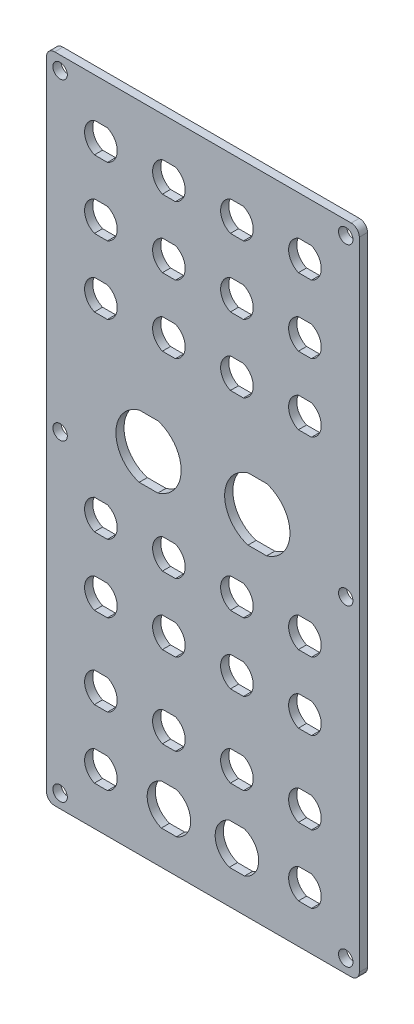
SolidWorks part; units mm, degrees
ref_plane "Front Plane" through (0, 0, 0) normal (0, 0, 1) x (1, 0, 0)
ref_plane "Top Plane" through (0, 0, 0) normal (0, 1, 0) x (1, 0, 0)
ref_plane "Right Plane" through (0, 0, 0) normal (1, 0, 0) x (0, 0, -1)
sketch "Sketch1" plane through (0, 0, 0) normal (0, 0, 1) x (1, 0, 0)
  line L1 (0, 0) -> (115, 0)
  line L2 (0, 0) -> (0, 240)
  line L3 (0, 240) -> (115, 240)
  line L4 (115, 0) -> (115, 240)
  dimension "D1" = 240
  dimension "D2" = 115
extrude "Boss-Extrude1" add sketch "Sketch1" along normal blind 3
sketch "Sketch2" plane through (0, 0, 3) normal (0, 0, 1) x (1, 0, 0)
  line L0 (20, 14.5) -> (20, 25.5) construction
  line L1 (22.3979, 25.5) -> (17.6021, 25.5)
  line L2 (22.3979, 14.5) -> (17.6021, 14.5)
  line L3 (0, 0) -> (115, 0) construction
  line L4 (0, 240) -> (0, 0) construction
  arc A0 (17.6021, 25.5) -> (17.6021, 14.5) centre (20, 20) ccw
  arc A1 (22.3979, 14.5) -> (22.3979, 25.5) centre (20, 20) ccw
  point P7 (20, 20)
  dimension "D2" = 12
  dimension "D1" = 11
  dimension "D3" = 20
  dimension "D4" = 20
extrude "Cut-Extrude1" cut sketch "Sketch2" against normal up to surface (3 mm away) up to face at (57.5, 120, 0)
pattern_linear "LPattern1" count 4 spacing 25 along (1, 0, 0) count 2 spacing 25 along (0, 1, 0) skipping (1, 0), (2, 0) of "Cut-Extrude1"
sketch "Sketch3" plane through (0, 0, 3) normal (0, 0, 1) x (1, 0, 0)
  line L0 (0, 120) -> (115, 120) construction
  line L1 (0, 240) -> (0, 0) construction
  line L2 (115, 0) -> (115, 240) construction
  line L3 (17.6021, 14.5) -> (22.3979, 14.5) construction
  line L4 (22.3979, 25.5) -> (17.6021, 25.5) construction
  line L5 (17.6021, 14.5) -> (22.3979, 14.5) construction
  line L6 (22.3979, 25.5) -> (17.6021, 25.5) construction
  line L7 (22.3979, 214.5) -> (17.6021, 214.5)
  line L8 (17.6021, 225.5) -> (22.3979, 225.5)
  arc A0 (17.6021, 25.5) -> (17.6021, 14.5) centre (20, 20) ccw construction
  arc A1 (22.3979, 14.5) -> (22.3979, 25.5) centre (20, 20) ccw construction
  arc A2 (17.6021, 25.5) -> (17.6021, 14.5) centre (20, 20) ccw construction
  arc A3 (22.3979, 14.5) -> (22.3979, 25.5) centre (20, 20) ccw construction
  arc A4 (22.3979, 225.5) -> (22.3979, 214.5) centre (20, 220) cw
  arc A5 (17.6021, 214.5) -> (17.6021, 225.5) centre (20, 220) cw
extrude "Cut-Extrude2" cut sketch "Sketch3" against normal up to surface (3 mm away) up to face at (95, 20, 0)
pattern_linear "LPattern2" count 4 spacing 25 along (1, 0, 0) count 3 spacing 25 along (0, -1, 0) of "Cut-Extrude2"
sketch "Sketch4" plane through (0, 0, 3) normal (0, 0, 1) x (1, 0, 0)
  line L0 (20, 25.5) -> (20, 14.5) construction
  line L1 (22.3979, 25.5) -> (17.6021, 25.5) construction
  line L2 (17.6021, 14.5) -> (22.3979, 14.5) construction
  line L3 (39, 45) -> (51, 45) construction
  line L4 (42.2161, 27.5) -> (47.7839, 27.5)
  line L5 (45, 12.5) -> (45, 27.5) construction
  line L6 (47.7839, 12.5) -> (42.2161, 12.5)
  arc A0 (42.2161, 27.5) -> (42.2161, 12.5) centre (45, 20) ccw
  arc A1 (42.6021, 50.5) -> (42.6021, 39.5) centre (45, 45) ccw construction
  arc A2 (47.3979, 39.5) -> (47.3979, 50.5) centre (45, 45) ccw construction
  arc A3 (47.7839, 12.5) -> (47.7839, 27.5) centre (45, 20) ccw
  point P16 (45, 45)
  point P17 (20, 20)
  point P24 (45, 20)
  point P25 (45, 14.7085)
  dimension "D1" = 16
  dimension "D2" = 15
extrude "Cut-Extrude3" cut sketch "Sketch4" against normal up to surface (3 mm away) up to face at (45, 220, 0)
ref_plane "Plane2" through (57.5, 0, 0) normal (-1, 0, 0) x (0, 0, 1)
mirror "Mirror2" about plane through (57.5, 0, 0) normal (-1, 0, 0) of "Cut-Extrude3"
sketch "Sketch5" plane through (0, 0, 3) normal (0, 0, 1) x (1, 0, 0)
  line L0 (14, 45) -> (26, 45) construction
  line L1 (22.3979, 80.5) -> (17.6021, 80.5)
  line L2 (20, 69.5) -> (20, 80.5) construction
  line L3 (17.6021, 69.5) -> (22.3979, 69.5)
  arc A0 (17.6021, 80.5) -> (17.6021, 69.5) centre (20, 75) ccw
  arc A1 (17.6021, 50.5) -> (17.6021, 39.5) centre (20, 45) ccw construction
  arc A2 (22.3979, 39.5) -> (22.3979, 50.5) centre (20, 45) ccw construction
  arc A3 (22.3979, 69.5) -> (22.3979, 80.5) centre (20, 75) ccw
  point P10 (20, 45)
  point P13 (20, 75.4328)
  point P18 (20, 75)
  dimension "D3" = 6
  dimension "D1" = 30
  dimension "D2" = 11
extrude "Cut-Extrude4" cut sketch "Sketch5" against normal up to surface (3 mm away) up to face at (45, 20, 0)
pattern_linear "LPattern3" count 4 spacing 25 along (1, 0, 0) count 2 spacing 25 along (0, 1, 0) of "Cut-Extrude4"
sketch "Sketch7" plane through (0, 0, 3) normal (0, 0, 1) x (1, 0, 0)
  line L0 (20, 100) -> (45, 100) construction
  line L1 (34.0722, 141.5) -> (40.9278, 141.5)
  line L2 (40.9278, 141.5) -> (40.9278, 118.5) construction
  line L3 (40.9278, 118.5) -> (34.0722, 118.5)
  line L4 (45, 100) -> (70, 100) construction
  arc A0 (34.0722, 141.5) -> (34.0722, 118.5) centre (37.5, 130) ccw
  arc A1 (40.9278, 118.5) -> (40.9278, 141.5) centre (37.5, 130) ccw
  point P1 (57.5, 100)
  dimension "D1" = 24
  dimension "D2" = 30
  dimension "D3" = 23
  dimension "D4" = 20
extrude "Cut-Extrude5" cut sketch "Sketch7" against normal up to surface (3 mm away) up to face at (45, 75, 0)
mirror "Mirror3" about plane through (57.5, 0, 0) normal (-1, 0, 0) of "Cut-Extrude5"
hole_wizard "M5 Clearance Hole1" positions "Sketch10" profile "Sketch11" hole size "M5" standard "ANSI Metric" end condition up to next
sketch "Sketch10" plane through (0, 0, 3) normal (0, 0, 1) x (1, 0, 0)
  line L12 (5, 235) -> (5, 5)
  line L13 (5, 5) -> (110, 5)
  line L14 (110, 5) -> (110, 235)
  line L15 (110, 235) -> (5, 235)
  line L16 (5, 235) -> (5, 5)
  line L17 (5, 5) -> (110, 5)
  line L18 (110, 5) -> (110, 235)
  line L19 (110, 235) -> (5, 235)
  point P25 (5, 235)
  point P26 (5, 5)
  point P27 (110, 5)
  point P28 (110, 235)
  point P31 (5, 120)
  point P37 (110, 120)
  dimension "D1" = 5
sketch "Sketch11" plane through (5, 235, 3) normal (1, 0, 0) x (0, -1, 0)
  line L0 (0, 0) -> (0, 3)
  line L1 (0, 3) -> (2.65, 3)
  line L2 (2.65, 3) -> (2.65, 0)
  line L5 (2.65, 0) -> (0, 0)
  line L11 (0, -6.35) -> (0, 107.95) construction
  dimension "Thru Hole Dia." = 5.3
  dimension "Thru Hole Depth" = 3
fillet "Fillet1" radius 3 4 edges at (0, 240, 1.5) (115, 240, 1.5) (115, 0, 1.5) (0, 0, 1.5)
